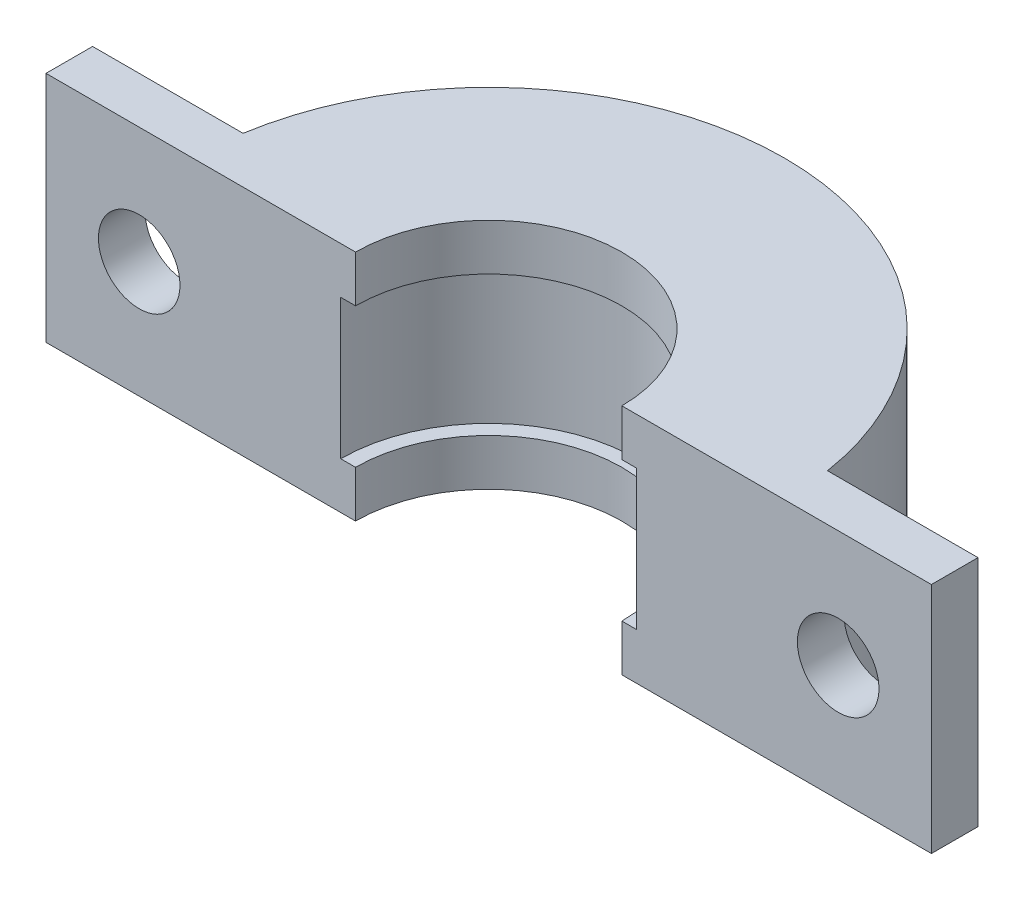
SolidWorks part; units mm, degrees
ref_plane "Front Plane" through (0, 0, 0) normal (0, 0, 1) x (1, 0, 0)
ref_plane "Top Plane" through (0, 0, 0) normal (0, 1, 0) x (1, 0, 0)
ref_plane "Right Plane" through (0, 0, 0) normal (1, 0, 0) x (0, 0, -1)
sketch "Sketch1" plane through (0, 0, 0) normal (0, 1, 0) x (1, 0, 0)
  line L0 (12.7, 0) -> (-12.7, 0)
  circle A0 centre (0, 0) radius 12.7
  circle A1 centre (0, 0) radius 5.715
  point P7 (0, 0)
  dimension "D1" = 25.4
  dimension "D2" = 11.43
extrude "Boss-Extrude1" add sketch "Sketch1" along normal mid plane 10 contours A1 L0 A0 region at (0, 0, -6.1428)
ref_plane "Plane1" through (0, 0, 0) normal (0, 1, 0) x (1, 0, 0)
sketch "Sketch2" plane through (0, 0, 0) normal (0, 1, 0) x (1, 0, 0)
  line L0 (-6.35, 0) -> (6.35, 0)
  circle A0 centre (0, 0) radius 6.35
  dimension "D1" = 12.7
extrude "Cut-Extrude1" cut sketch "Sketch2" against normal mid plane 6 contours L0 A0 region at (0, 0, -2.695)
sketch "Sketch3" plane through (0, 0, 0) normal (0, 0, 1) x (1, 0, 0)
  line L0 (0, -5) -> (0, 5) construction
  line L2 (5.715, 5) -> (-5.715, 5) construction
  line L3 (6.985, 0) -> (-6.985, 0) construction
  line L4 (-11, -5) -> (-19, -5)
  line L5 (-11, -5) -> (-11, 5)
  line L6 (-11, 5) -> (-19, 5)
  line L7 (-19, -5) -> (-19, 5)
  line L8 (-11, -5) -> (-19, 5) construction
  line L9 (-11, 5) -> (-19, -5) construction
  line L11 (-5.715, -5) -> (-12.7, -5) construction
  line L13 (-12.7, 5) -> (-12.7, -5) construction
  line L14 (11, 5) -> (19, 5)
  line L15 (19, -5) -> (19, 5)
  line L16 (11, -5) -> (19, -5)
  line L17 (11, -5) -> (11, 5)
  circle A0 centre (-15, 0) radius 1.75
  circle A1 centre (15, 0) radius 1.75
  point P0 (-15, 0)
  point P4 (0, 0)
  dimension "D2" = 3.5
  dimension "D1" = 8
  dimension "D3" = 1.7
extrude "Boss-Extrude2" add sketch "Sketch3" against normal blind 2
